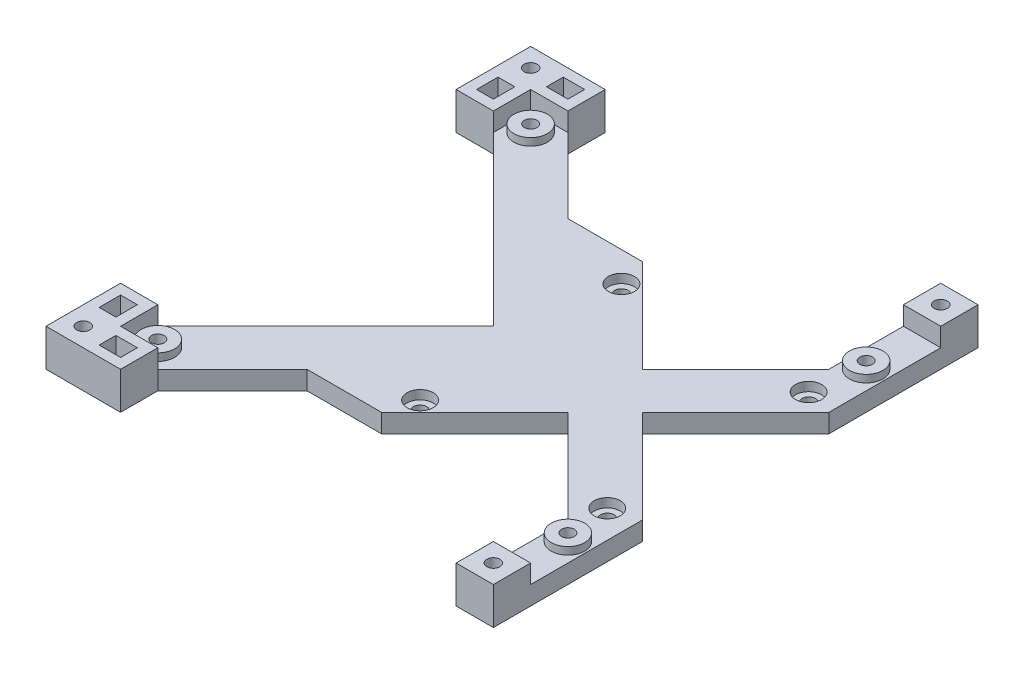
SolidWorks part; units mm, degrees
ref_plane "Plan de face" through (0, 0, 0) normal (0, 0, 1) x (1, 0, 0)
ref_plane "Plan de dessus" through (0, 0, 0) normal (0, 1, 0) x (1, 0, 0)
ref_plane "Plan de droite" through (0, 0, 0) normal (1, 0, 0) x (0, 0, -1)
sketch "Esquisse1" plane through (0, 0, 0) normal (0, 1, 0) x (1, 0, 0)
  line L0 (55, 35) -> (-10.084, 35) construction
  line L1 (55, 35) -> (55, -35) construction
  line L2 (55, -35) -> (-10.084, -35) construction
  line L3 (-10.084, 35) -> (-10.084, -35) construction
  line L4 (-10.084, 35) -> (55, -35) construction
  line L5 (55, 35) -> (-10.084, -35) construction
  line L6 (-25, -35) -> (-5, -35)
  line L7 (-55, -55) -> (55, -55) construction
  line L8 (-55, -55) -> (-55, 55) construction
  line L9 (-55, 55) -> (55, 55) construction
  line L10 (55, -55) -> (55, 55) construction
  line L11 (-55, -55) -> (55, 55) construction
  line L12 (-55, 55) -> (55, -55) construction
  line L13 (-25, -35) -> (-45, -55)
  line L14 (-45, -55) -> (-55, -55)
  line L15 (-55, -55) -> (-55, -45)
  line L16 (-55, -45) -> (-10.084, -0.084)
  line L17 (55, -35) -> (55, -25)
  line L18 (-5, -35) -> (20, -10)
  line L19 (20, -10) -> (45, -35)
  line L21 (55, -25) -> (30, 0)
  line L22 (-10.084, -0.084) -> (-10.084, 0.084)
  line L23 (-10.084, 0) -> (30, 0) construction
  line L24 (55, 25) -> (30, 0)
  line L25 (55, 35) -> (55, 25)
  line L27 (20, 10) -> (45, 35)
  line L28 (-5, 35) -> (20, 10)
  line L29 (-25, 35) -> (-5, 35)
  line L30 (-25, 35) -> (-45, 55)
  line L31 (-45, 55) -> (-55, 55)
  line L32 (-55, 55) -> (-55, 45)
  line L33 (-55, 45) -> (-10.084, 0.084)
  line L34 (45, 35) -> (45, 55)
  line L35 (45, 55) -> (55, 55)
  line L36 (55, 55) -> (55, 35)
  line L37 (45, -35) -> (45, -55)
  line L38 (45, -55) -> (55, -55)
  line L39 (55, -35) -> (55, -55)
  circle A0 centre (-50, 50) radius 1.65 construction
  circle A1 centre (-50, -50) radius 1.65 construction
  circle A2 centre (50, -40) radius 1.65 construction
  circle A3 centre (50, 40) radius 1.65 construction
  point P4 (0, 0)
  point P37 (0, 0)
  dimension "D1" = 10
  dimension "D2" = 10
  dimension "D3" = 10
  dimension "D4" = 10
  dimension "D5" = 90
  dimension "D6" = 90
  dimension "D7" = 90
  dimension "D8" = 90
  dimension "D10" = 0
  dimension "D11" = 110
  dimension "D12" = 110
  dimension "D13" = 0
extrude "Boss.-Extru.1" add sketch "Esquisse1" along normal blind 5
sketch "Esquisse2" plane through (0, 0, 0) normal (0, 1, 0) x (1, 0, 0)
  line L0 (-55, -45) -> (-65, -45)
  line L1 (-65, -45) -> (-65, -65)
  line L2 (-65, -65) -> (-45, -65)
  line L3 (-45, -65) -> (-45, -55)
  line L4 (0, 0) -> (-80.1465, 0) construction
  line L5 (-55, -45) -> (-55, -55)
  line L14 (-55, -55) -> (-45, -55)
  line L19 (-45, 65) -> (-45, 55)
  line L20 (-65, 65) -> (-45, 65)
  line L21 (-65, 45) -> (-65, 65)
  line L22 (-55, 55) -> (-45, 55)
  line L23 (-55, 45) -> (-55, 55)
  line L24 (-55, 45) -> (-65, 45)
  line L25 (55, 55) -> (45, 55) construction
  line L26 (45, 55) -> (55, 55)
  line L27 (45, 55) -> (45, 65)
  line L28 (45, 65) -> (55, 65)
  line L29 (55, 55) -> (55, 65)
  line L30 (45, -55) -> (55, -55)
  line L31 (45, -55) -> (45, -65)
  line L32 (45, -65) -> (55, -65)
  line L33 (55, -55) -> (55, -65)
  line L34 (55, -55) -> (55, -25) construction
  line L35 (55, 25) -> (55, 55) construction
  line L36 (-55, 55) -> (-65, 65) construction
  line L37 (-55, -55) -> (-65, -65) construction
  line L39 (-65, -55) -> (-55, -65) construction
  line L40 (-65, 55) -> (-55, 65) construction
  point P40 (-65, -55)
  dimension "D1" = 10
  dimension "D2" = 90
  dimension "D3" = 10
  dimension "D4" = 10
  dimension "D5" = 10
  dimension "D6" = 0
  dimension "D7" = 0
extrude "Boss.-Extru.2" add sketch "Esquisse2" along normal blind 10
sketch "Esquisse3" plane through (0, 5, 0) normal (0, 1, 0) x (1, 0, 0)
  line L0 (0, 0) -> (50, 40) construction
  line L1 (0, 0) -> (50, -40) construction
  line L2 (0, 0) -> (-50, 50) construction
  line L3 (0, 0) -> (-50, -50) construction
  circle A0 centre (-50, -50) radius 4.5
  circle A1 centre (-50, 50) radius 4.5
  circle A2 centre (50, 40) radius 4.5
  circle A3 centre (50, -40) radius 4.5
  dimension "D9" = 9
  dimension "D10" = 9
  dimension "D11" = 9
  dimension "D12" = 9
  dimension "D1" = 50
  dimension "D2" = 40
  dimension "D3" = 40
  dimension "D4" = 50
  dimension "D5" = 50
  dimension "D6" = 50
  dimension "D7" = 50
  dimension "D8" = 50
extrude "Boss.-Extru.3" add sketch "Esquisse3" along normal blind 2
sketch "Esquisse5" plane through (0, 7, 0) normal (0, 1, 0) x (1, 0, 0)
  point P0 (-50, 50)
  point P1 (50, 40)
  point P3 (50, -40)
  point P5 (-50, -50)
hole_wizard "Dégagement M31" positions "Esquisse3D2" profile "Esquisse6" hole size "M3" standard "Ansi Metric" end condition through all
sketch3d "Esquisse3D2"
  point P0 (-50, 7, -50)
  point P3 (50, 7, -40)
  point P6 (50, 7, 40)
  point P9 (-50, 7, 50)
sketch "Esquisse6" plane through (-50, 7, -50) normal (1, 0, 0) x (0, 0, 1)
  line L0 (0, 0) -> (0, 7)
  line L1 (0, 7) -> (1.7, 7)
  line L2 (1.7, 7) -> (1.7, 0)
  line L5 (1.7, 0) -> (0, 0)
  line L11 (0, -6.35) -> (0, 107.95) construction
  dimension "Diamètre du perçage jusqu'au prochain" = 3.4
  dimension "Profondeur du perçage jusqu'au prochain" = 7
sketch "Esquisse7" plane through (0, 5, 0) normal (0, 1, 0) x (1, 0, 0)
  line L0 (-10.084, 0.084) -> (-10.084, -0.084) construction
  line L1 (-10.084, -35) -> (55, -35) construction
  line L2 (-10.084, -35) -> (-10.084, 35) construction
  line L3 (-10.084, 35) -> (55, 35) construction
  line L4 (55, -35) -> (55, 35) construction
  line L5 (55, 25) -> (55, 55) construction
  line L6 (-5, 35) -> (-25, 35) construction
  line L7 (-25, -35) -> (-5, -35) construction
  line L8 (-10.084, 35) -> (55, -35) construction
  line L9 (-10.084, -35) -> (55, 35) construction
  point P5 (47.5618, 27)
  point P14 (47.5618, -27)
  point P15 (-2.6458, -27)
  point P22 (-2.6458, 27)
  dimension "D1" = 0
  dimension "D2" = 0
  dimension "D3" = 0
  dimension "D4" = 0
  dimension "D5" = 54
  dimension "D6" = 27
  dimension "D7" = 27
hole_wizard "Chambrage pour vis à tête ronde bombée M32" positions "Esquisse3D3" profile "Esquisse8" counterbore size "M3" standard "Ansi Metric" end condition through all
sketch3d "Esquisse3D3"
  point P0 (-2.6458, 5, -27)
  point P3 (-2.6458, 5, 27)
  point P6 (47.5618, 5, 27)
  point P9 (47.5618, 5, -27)
sketch "Esquisse8" plane through (-2.6458, 5, -27) normal (1, 0, 0) x (0, 0, 1)
  line L0 (0, 0) -> (0, 5)
  line L1 (0, 5) -> (1.8, 5)
  line L3 (1.8, 5) -> (1.8, 2.4)
  line L4 (1.8, 2.4) -> (3.5, 2.4)
  line L5 (3.5, 2.4) -> (3.5, 0)
  line L7 (3.5, 0) -> (0, 0)
  line L11 (0, -6.35) -> (0, 107.95) construction
  dimension "Diamètre du perçage jusqu'au prochain" = 3.6
  dimension "Profondeur du perçage jusqu'au prochain" = 5
  dimension "Diamètre du chambrage" = 7
  dimension "Profondeur du chambrage" = 2.4
sketch "Esquisse10" plane through (0, 0, 0) normal (0, 1, 0) x (1, 0, 0)
  line L24 (-55, -55) -> (55, -55) construction
  line L29 (-55, -55) -> (-55, 55) construction
  line L30 (-55, 55) -> (55, 55) construction
  line L31 (55, 55) -> (55, -55) construction
  line L39 (-55, 55) -> (-45, 55) construction
  line L50 (-55, 55) -> (-55, 45) construction
  line L70 (108.7528, -114.7101) -> (134.7336, -99.7101) construction
  line L71 (-76.0746, 22) -> (-74.4346, 22) construction
  line L72 (-76.0746, 22) -> (-76.0746, -8) construction
  line L73 (-76.0746, -8) -> (-74.4346, -8) construction
  line L74 (-74.4346, 22) -> (-74.4346, -8) construction
  line L75 (115.271, -110) -> (115.271, 110) construction
  line L76 (115.271, 110) -> (-75.2546, 0) construction
  line L77 (-75.2546, 0) -> (115.271, -110) construction
  line L82 (134.7336, -99.7101) -> (133.9136, -98.2899) construction
  line L83 (133.9136, -98.2899) -> (107.9328, -113.2899) construction
  line L84 (107.9328, -113.2899) -> (108.7528, -114.7101) construction
  line L85 (108.7364, 114.6873) -> (131.2036, 94.807) construction
  line L86 (131.2036, 94.807) -> (132.2903, 96.0352) construction
  line L87 (132.2903, 96.0352) -> (109.8232, 115.9155) construction
  line L88 (109.8232, 115.9155) -> (108.7364, 114.6873) construction
  circle A4 centre (-75.2546, 0) radius 5 construction
  circle A5 centre (115.271, 110) radius 5 construction
  circle A6 centre (115.271, -110) radius 5 construction
  circle A7 centre (120.91, -126.83) radius 3.15 construction
  circle A8 centre (157, -129.7) radius 3.15 construction
  circle A9 centre (120.91, 126.83) radius 3.15 construction
  circle A10 centre (157, 129.7) radius 3.15 construction
  circle A11 centre (51.7625, 0) radius 63.5085 construction
  dimension "D9" = 5.639
  dimension "D12" = 16.83
  dimension "D13" = 5.639
  dimension "D14" = 36.09
  dimension "D27" = 8
  dimension "D31" = 1.64
  dimension "D32" = 0.82
  dimension "D33" = 8
  dimension "D1" = 60.271
  dimension "D2" = 106.7625
  dimension "D3" = 60
  dimension "D4" = 60
  dimension "D5" = 60
  dimension "D6" = 110
  dimension "D7" = 110
  dimension "D8" = 16.83
  dimension "D10" = 36.09
  dimension "D11" = 2.87
  dimension "D15" = 2.87
  dimension "D16" = 0
  dimension "D17" = 0
  dimension "D18" = 0
  dimension "D19" = 0
  dimension "D20" = 1.64
  dimension "D21" = 8
  dimension "D22" = 0.82
  dimension "D23" = 1.64
  dimension "D24" = 30
  dimension "D25" = 30
  dimension "D26" = 51.7625
  dimension "D28" = 0.82
  dimension "D29" = 60
  dimension "D30" = 30
sketch "Esquisse11" plane through (0, 10, 0) normal (0, 1, 0) x (1, 0, 0)
  line L0 (-55, -55) -> (-65, -65) construction
  line L1 (-55, 55) -> (-65, 65) construction
  line L2 (55, 65) -> (45, 55) construction
  line L3 (45, -55) -> (55, -65) construction
  circle A0 centre (-60, 60) radius 1.75
  circle A1 centre (50, 60) radius 1.75
  circle A2 centre (50, -60) radius 1.75
  circle A3 centre (-60, -60) radius 1.75
  dimension "D1" = 3.5
  dimension "D2" = 3.5
  dimension "D3" = 3.5
  dimension "D4" = 3.5
extrude "Enlèv. mat.-Extru.1" cut sketch "Esquisse11" against normal blind 10
sketch "Esquisse14" plane through (0, 10, 0) normal (0, 1, 0) x (1, 0, 0)
  line L0 (-55, 55) -> (55, 55) construction
  line L1 (-53.5, 57.75) -> (-47.75, 57.75)
  line L2 (-53.5, 57.75) -> (-53.5, 62.25)
  line L3 (-53.5, 62.25) -> (-47.75, 62.25)
  line L4 (-47.75, 57.75) -> (-47.75, 62.25)
  line L5 (-62.25, 53.5) -> (-57.75, 53.5)
  line L6 (-62.25, 53.5) -> (-62.25, 47.75)
  line L7 (-62.25, 47.75) -> (-57.75, 47.75)
  line L8 (-57.75, 53.5) -> (-57.75, 47.75)
  line L9 (-45, 65) -> (-65, 65) construction
  line L10 (-55, -55) -> (-55, 55) construction
  line L11 (-65, 65) -> (-65, 45) construction
  line L12 (-65, 45) -> (-55, 45) construction
  line L13 (-45, 55) -> (-45, 65) construction
  line L14 (0, 0) -> (-92.4316, 0) construction
  line L15 (-57.75, -53.5) -> (-57.75, -47.75)
  line L16 (-62.25, -47.75) -> (-57.75, -47.75)
  line L17 (-62.25, -53.5) -> (-62.25, -47.75)
  line L18 (-62.25, -53.5) -> (-57.75, -53.5)
  line L19 (-47.75, -57.75) -> (-47.75, -62.25)
  line L20 (-53.5, -62.25) -> (-47.75, -62.25)
  line L21 (-53.5, -57.75) -> (-53.5, -62.25)
  line L22 (-53.5, -57.75) -> (-47.75, -57.75)
  point P18 (-60, 45)
  dimension "D1" = 2.75
  dimension "D2" = 2.75
  dimension "D3" = 2.75
  dimension "D4" = 2.75
  dimension "D5" = 2.75
  dimension "D6" = 2.75
  dimension "D7" = 1.5
  dimension "D8" = 1.5
extrude "Enlèv. mat.-Extru.2" cut sketch "Esquisse14" against normal blind 5
